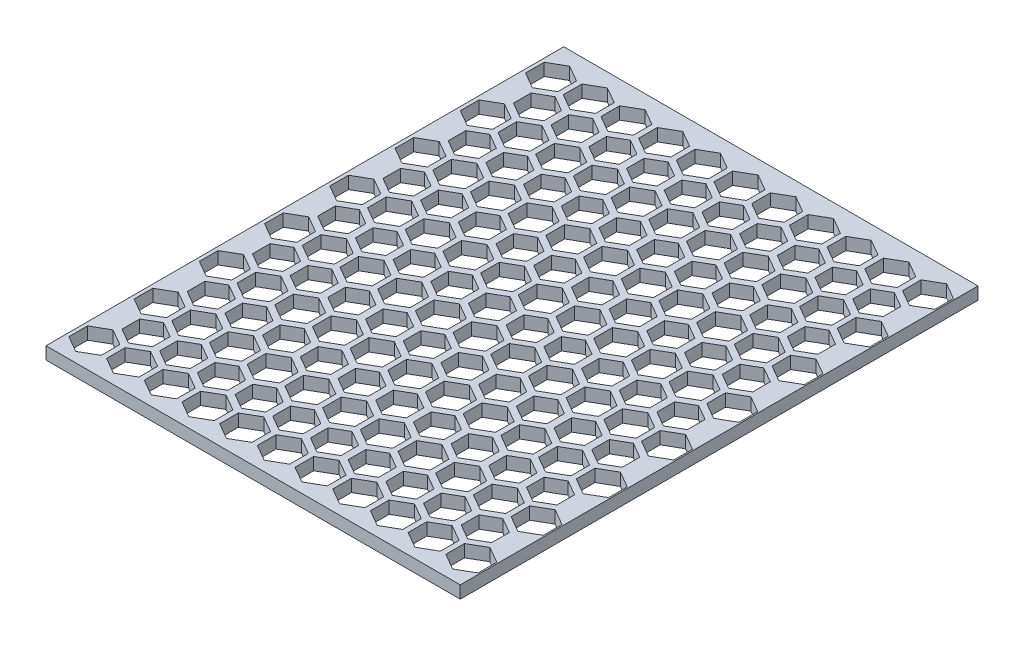
SolidWorks part; units mm, degrees
ref_plane "Front Plane" through (0, 0, 0) normal (0, 0, 1) x (1, 0, 0)
ref_plane "Top Plane" through (0, 0, 0) normal (0, 1, 0) x (1, 0, 0)
ref_plane "Right Plane" through (0, 0, 0) normal (1, 0, 0) x (0, 0, -1)
sketch "Sketch1" plane through (0, 0, 0) normal (0, 1, 0) x (1, 0, 0)
  line L1 (0.3767, 13.3847) -> (20.3767, 13.3847)
  line L2 (0.3767, 13.3847) -> (0.3767, -11.6153)
  line L3 (0.3767, -11.6153) -> (20.3767, -11.6153)
  line L4 (20.3767, 13.3847) -> (20.3767, -11.6153)
  dimension "D1" = 25
  dimension "D2" = 20
extrude "Boss-Extrude1" add sketch "Sketch1" along normal blind 0.6
sketch "Sketch3" plane through (0, 0.6, 0) normal (0, 1, 0) x (1, 0, 0)
  line L0 (20.3767, -11.6153) -> (20.3767, 13.3847) construction
  line L1 (20.31, -9.7842) -> (19.5302, -9.334)
  line L2 (19.5302, -9.334) -> (18.7505, -9.7842)
  line L3 (18.7505, -9.7842) -> (18.7505, -10.6845)
  line L4 (18.7505, -10.6845) -> (19.5302, -11.1347)
  line L5 (19.5302, -11.1347) -> (20.31, -10.6845)
  line L6 (20.31, -10.6845) -> (20.31, -9.7842)
  circle A0 centre (19.5302, -10.2343) radius 0.7797 construction
extrude "Cut-Extrude4" cut sketch "Sketch3" against normal blind 0.6 contours L1 L2 L3 L4 L5 L6
pattern_linear "LPattern1" count 11 spacing 1.82 along (-1, 0, 0) count 8 spacing 3.15 along (0, 0, -1) of "Cut-Extrude4"
sketch "Sketch4" plane through (0, 0.6, 0) normal (0, 1, 0) x (1, 0, 0)
  line L1 (18.6342, -7.8125) -> (17.8981, -8.2375)
  line L2 (17.8981, -8.2375) -> (17.8981, -9.0875)
  line L3 (17.8981, -9.0875) -> (18.6342, -9.5125)
  line L4 (18.6342, -9.5125) -> (19.3703, -9.0875)
  line L5 (19.3703, -9.0875) -> (19.3703, -8.2375)
  line L6 (19.3703, -8.2375) -> (18.6342, -7.8125)
  circle A0 centre (18.6342, -8.6625) radius 0.7361 construction
  dimension "D1" = 1.7
extrude "Cut-Extrude5" cut sketch "Sketch4" against normal blind 0.6
pattern_linear "LPattern2" count 10 spacing 1.82 along (-1, 0, 0) count 7 spacing 3.15 along (0, 0, -1) of "Cut-Extrude5"
